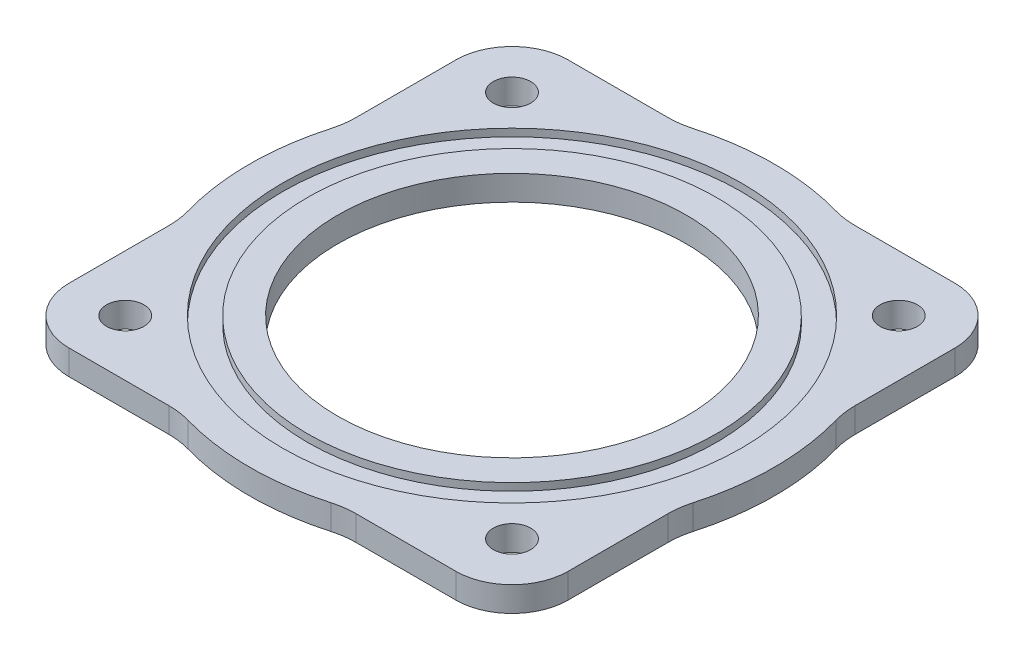
SolidWorks part; units mm, degrees
ref_plane "Front Plane" through (0, 0, 0) normal (0, 0, 1) x (1, 0, 0)
ref_plane "Top Plane" through (0, 0, 0) normal (0, 1, 0) x (1, 0, 0)
ref_plane "Right Plane" through (0, 0, 0) normal (1, 0, 0) x (0, 0, -1)
sketch "Sketch1" plane through (0, 0, 0) normal (0, 1, 0) x (1, 0, 0)
  line L0 (0, 43.6291) -> (0, 56.3563)
  line L1 (7.1437, 0) -> (19.8709, 0)
  line L2 (0, 7.1437) -> (0, 19.8709)
  line L3 (7.1437, 63.5) -> (19.8709, 63.5)
  line L4 (63.5, 7.1437) -> (63.5, 19.8709)
  line L5 (43.6291, 63.5) -> (56.3563, 63.5)
  line L6 (63.5, 43.6291) -> (63.5, 56.3563)
  line L7 (43.6291, 0) -> (56.3563, 0)
  circle A0 centre (31.75, 31.75) radius 22.1742
  circle A1 centre (56.3563, 56.3563) radius 2.3812
  circle A2 centre (56.3563, 7.1437) radius 2.3812
  circle A3 centre (7.1437, 7.1437) radius 2.3812
  circle A4 centre (7.1437, 56.3563) radius 2.3812
  arc A7 (7.1437, 63.5) -> (0, 56.3563) centre (7.1437, 56.3563) ccw
  arc A8 (56.3563, 0) -> (63.5, 7.1437) centre (56.3563, 7.1437) ccw
  arc A9 (0, 7.1437) -> (7.1437, 0) centre (7.1437, 7.1437) ccw
  arc A10 (63.5, 56.3563) -> (56.3563, 63.5) centre (56.3563, 56.3563) ccw
  arc A11 (-0.3851, 40.8585) -> (-0.3851, 22.6415) centre (31.75, 31.75) ccw
  arc A12 (22.6415, -0.3851) -> (40.8585, -0.3851) centre (31.75, 31.75) ccw
  arc A13 (40.8585, 63.8851) -> (22.6415, 63.8851) centre (31.75, 31.75) ccw
  arc A14 (63.8851, 22.6415) -> (63.8851, 40.8585) centre (31.75, 31.75) ccw
  arc A15 (63.8851, 40.8585) -> (63.5, 43.6291) centre (73.66, 43.6291) cw
  arc A16 (63.5, 19.8709) -> (63.8851, 22.6415) centre (73.66, 19.8709) cw
  arc A17 (40.8585, -0.3851) -> (43.6291, 0) centre (43.6291, -10.16) cw
  arc A18 (22.6415, -0.3851) -> (19.8709, 0) centre (19.8709, -10.16) ccw
  arc A19 (0, 19.8709) -> (-0.3851, 22.6415) centre (-10.16, 19.8709) ccw
  arc A20 (-0.3851, 40.8585) -> (0, 43.6291) centre (-10.16, 43.6291) ccw
  arc A21 (22.6415, 63.8851) -> (19.8709, 63.5) centre (19.8709, 73.66) cw
  arc A22 (43.6291, 63.5) -> (40.8585, 63.8851) centre (43.6291, 73.66) cw
  point P16 (63.5, 42.1213)
  point P31 (63.5, 21.3787)
  point P34 (42.1213, 0)
  point P41 (0, 42.1213)
  point P46 (42.1213, 63.5)
  dimension "D3" = 44.3484
  dimension "D6" = 4.7625
  dimension "D7" = 4.7625
  dimension "D8" = 4.7625
  dimension "D9" = 4.7625
  dimension "D10" = 7.1437
  dimension "D11" = 7.1437
  dimension "D12" = 7.1437
  dimension "D13" = 7.1437
  dimension "D14" = 7.1437
  dimension "D15" = 7.1437
  dimension "D16" = 7.1437
  dimension "D17" = 7.1437
  dimension "D18" = 49.2125
  dimension "D2" = 10.16
  dimension "D19" = 11.2268
  dimension "D4" = 31.75
  dimension "D5" = 31.75
extrude "Boss-Extrude1" add sketch "Sketch1" against normal blind 3.175
sketch "Sketch2" plane through (0, 0, 0) normal (0, 1, 0) x (1, 0, 0)
  circle A0 centre (31.75, 31.75) radius 26.035
  circle A1 centre (31.75, 31.75) radius 29.21
  dimension "D1" = 52.07
  dimension "D2" = 58.42
extrude "Cut-Extrude1" cut sketch "Sketch2" against normal blind 0.9525
